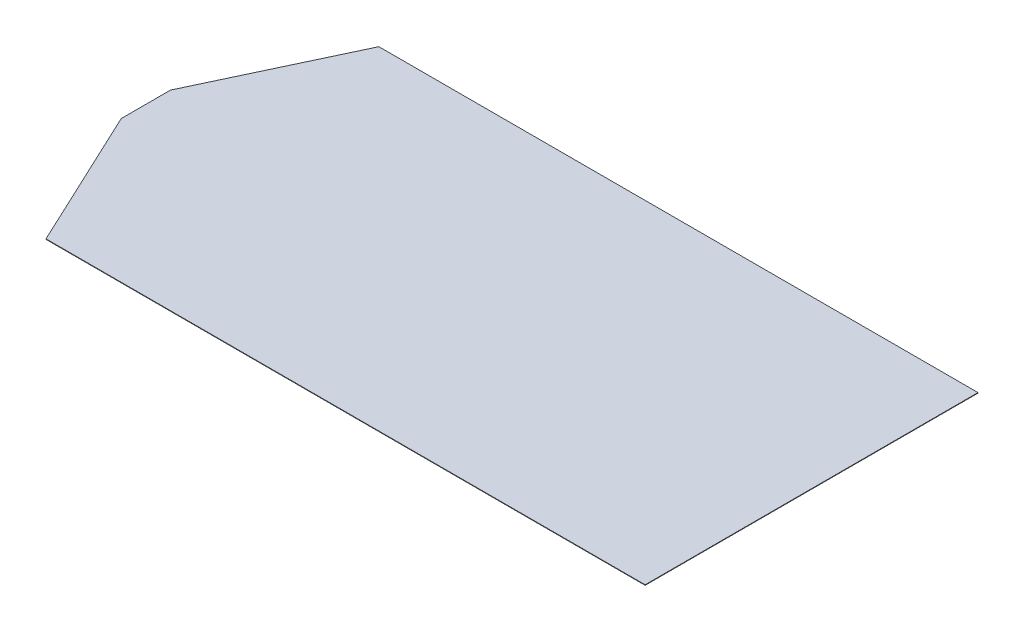
SolidWorks part; units mm, degrees
material "DX51D+Z"
ref_plane "Frontale" through (0, 0, 0) normal (0, 0, 1) x (1, 0, 0)
ref_plane "Superiore" through (0, 0, 0) normal (0, 1, 0) x (1, 0, 0)
ref_plane "Destro" through (0, 0, 0) normal (1, 0, 0) x (0, 0, -1)
sketch "Schizzo1" plane through (0, 0, 0) normal (0, 1, 0) x (1, 0, 0)
  line L0 (-900, 500) -> (-1100, 74)
  line L1 (-900, -500) -> (900, -500)
  line L2 (-900, -500) -> (-900, 500) construction
  line L3 (-900, 500) -> (900, 500)
  line L4 (900, -500) -> (900, 500)
  line L5 (-900, -500) -> (900, 500) construction
  line L6 (-900, 500) -> (900, -500) construction
  line L7 (-1100, 74) -> (-1100, -74)
  line L8 (-1100, -74) -> (-900, -500)
  line L9 (-1100, 0) -> (-900, 0) construction
  line L10 (-100, 500) -> (-100, -500) construction
  line L11 (400, 500) -> (400, -500) construction
  point P0 (0, 0)
  dimension "D1" = 2000
  dimension "D2" = 1000
  dimension "D3" = 200
  dimension "D4" = 148
  dimension "D5" = 500
  dimension "D6" = 500
base flange "Base-Flangia1" sketch "Schizzo1" thickness 1.5 reverse thickness direction no parameters "D1"=3
sketch "Linee di piegatura1" [suppressed] plane through (0, 0, 0) normal (0, 1, 0) x (1, 0, 0)
sketch "Casella di contorno1" [suppressed] plane through (0, 0, 0) normal (0, 1, 0) x (1, 0, 0)
sheet metal parameters "Lamiera1" thickness 1.5 parameters "D1"=3
flat pattern "Ripetizione piatta1" [suppressed]
sketch "Linee di piegatura2" plane through (0, 0, 0) normal (0, 1, 0) x (1, 0, 0)
sketch3d "Casella di contorno2" [suppressed]
  line L0 (900, 500, 0) -> (-1100, 500, 0) construction
  line L1 (900, -500, 0) -> (-1100, -500, 0) construction
  line L2 (900, 500, 0) -> (900, -500, 0) construction
  line L3 (-1100, 500, 0) -> (-1100, -500, 0) construction
